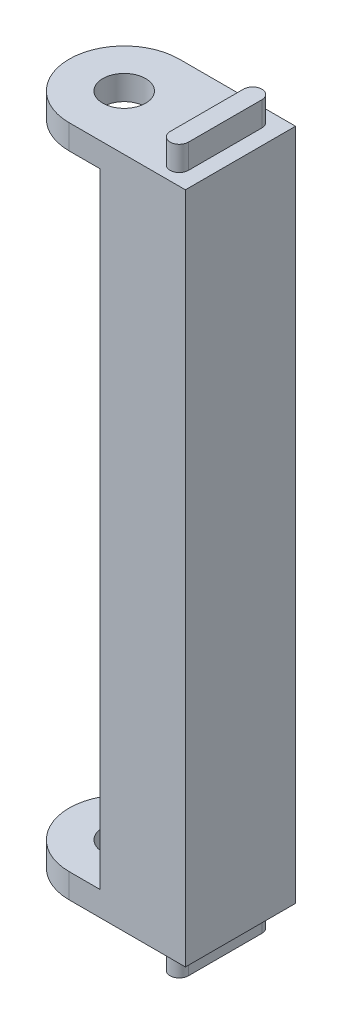
SolidWorks part; units mm, degrees
ref_plane "Front Plane" through (0, 0, 0) normal (0, 0, 1) x (1, 0, 0)
ref_plane "Top Plane" through (0, 0, 0) normal (0, 1, 0) x (1, 0, 0)
ref_plane "Right Plane" through (0, 0, 0) normal (1, 0, 0) x (0, 0, -1)
sketch "Sketch1" plane through (0, 0, 0) normal (0, 1, 0) x (1, 0, 0)
  line L0 (-2.5, 0) -> (2.5, 0) construction
  line L5 (-2.5, 4.5) -> (2.509, 4.5)
  line L6 (-2.5, -4.5) -> (2.509, -4.5)
  line L8 (7, -4.5) -> (7, 4.5)
  line L10 (7, 4.5) -> (2.509, 4.5)
  line L12 (7, -4.5) -> (7, 4.5)
  line L14 (7, -4.5) -> (2.509, -4.5)
  line L15 (5, 3) -> (5, -3) construction
  line L16 (5.75, 3) -> (5.75, -3)
  line L17 (4.25, 3) -> (4.25, -3)
  arc A1 (-2.5, 4.5) -> (-2.5, -4.5) centre (-2.5, 0) ccw
  circle A3 centre (-2.5, 0) radius 1.75
  arc A4 (0.0045, 4.5) -> (0.0045, -4.5) centre (-2.5, 0) cw
  arc A5 (5.75, 3) -> (4.25, 3) centre (5, 3) ccw
  arc A6 (4.25, -3) -> (5.75, -3) centre (5, -3) ccw
  point P2 (0, 0)
  point P7 (5, 0)
  point P22 (7, 0)
  point P25 (-7, 0)
  dimension "D2" = 9.5
  dimension "D3" = 3.5
  dimension "D6" = 5.15
  dimension "D8" = 1.5
  dimension "D9" = 6
  dimension "D10" = 14
  dimension "D1" = 9
  dimension "D4" = 5
  dimension "D5" = 2.5
  dimension "D7" = 2
extrude "Boss-Extrude3" add sketch "Sketch1" along normal blind 2 contours A4 L5 A1 L6 A3 | L5 A4 L6 L14 L8 L10 A6 L17 A5 L16 | L17 A6 L16 A5 region at (-1.2478, 0, -4.368) region at (4.2023, 0, 0) region at (5, 0, 0)
extrude "Boss-Extrude4" add sketch "Sketch1<3>" against normal blind 25.5 contours L5 A4 L6 L14 L8 L10 A6 L17 A5 L16 | L17 A6 L16 A5 region at (4.2023, 0, 0) region at (5, 0, 0)
sketch "Sketch1<3>" plane through (0, 0, 0) normal (0, 1, 0) x (1, 0, 0) same geometry as "Sketch1"
extrude "Boss-Extrude5" add sketch "Sketch1<5>" along normal blind 4 contours L17 A6 L16 A5 region at (5, 0, 0)
sketch "Sketch1<5>" plane through (0, 0, 0) normal (0, 1, 0) x (1, 0, 0) same geometry as "Sketch1"
mirror "Mirror1" about plane through (0, -25.5, 0) normal (0, 1, 0) of bodies 111
